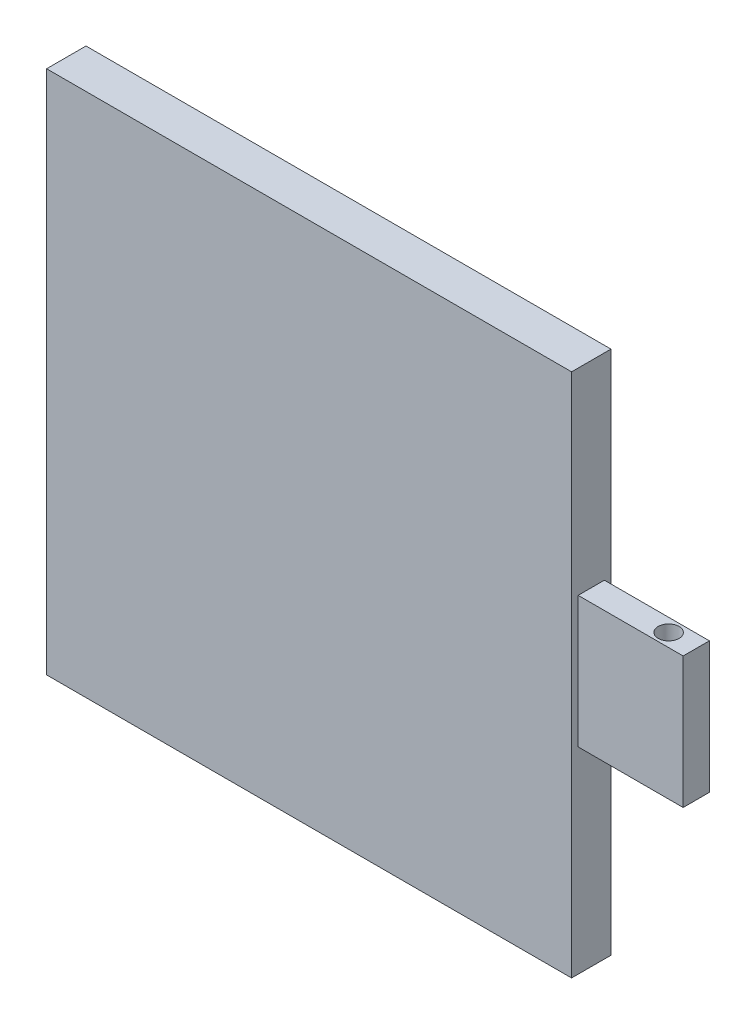
SolidWorks part; units mm, degrees
ref_plane "Front Plane" through (0, 0, 0) normal (0, 0, 1) x (1, 0, 0)
ref_plane "Top Plane" through (0, 0, 0) normal (0, 1, 0) x (1, 0, 0)
ref_plane "Right Plane" through (0, 0, 0) normal (1, 0, 0) x (0, 0, -1)
sketch "Sketch1" plane through (0, 0, 0) normal (0, 0, 1) x (1, 0, 0)
  line L1 (-26.749, 19.5473) -> (13.251, 19.5473)
  line L2 (-26.749, 19.5473) -> (-26.749, -20.4527)
  line L3 (-26.749, -20.4527) -> (13.251, -20.4527)
  line L4 (13.251, 19.5473) -> (13.251, -20.4527)
  dimension "D1" = 40
  dimension "D2" = 40
extrude "Boss-Extrude1" add sketch "Sketch1" along normal blind 3
sketch "Sketch6" plane through (13.251, 0, 0) normal (1, 0, 0) x (0, 0, -1)
  line L0 (-3, 19.5473) -> (0, 19.5473) construction
  line L1 (-2.5, 4.5473) -> (-0.5, 4.5473)
  line L2 (-2.5, 4.5473) -> (-2.5, -5.4527)
  line L3 (-2.5, -5.4527) -> (-0.5, -5.4527)
  line L4 (-0.5, 4.5473) -> (-0.5, -5.4527)
  line L5 (-3, -20.4527) -> (0, -20.4527) construction
  line L6 (0, -20.4527) -> (0, 19.5473) construction
  line L7 (-3, -20.4527) -> (-3, 19.5473) construction
  dimension "D1" = 15
  dimension "D2" = 15
  dimension "D3" = 0.5
  dimension "D4" = 0.5
extrude "Boss-Extrude4" add sketch "Sketch6" along normal blind 8
sketch "Sketch7" plane through (0, -5.4527, 0) normal (0, -1, 0) x (1, 0, 0)
  circle A0 centre (19.1457, 1.5) radius 0.7944
extrude "Cut-Extrude1" cut sketch "Sketch7" against normal up to next
